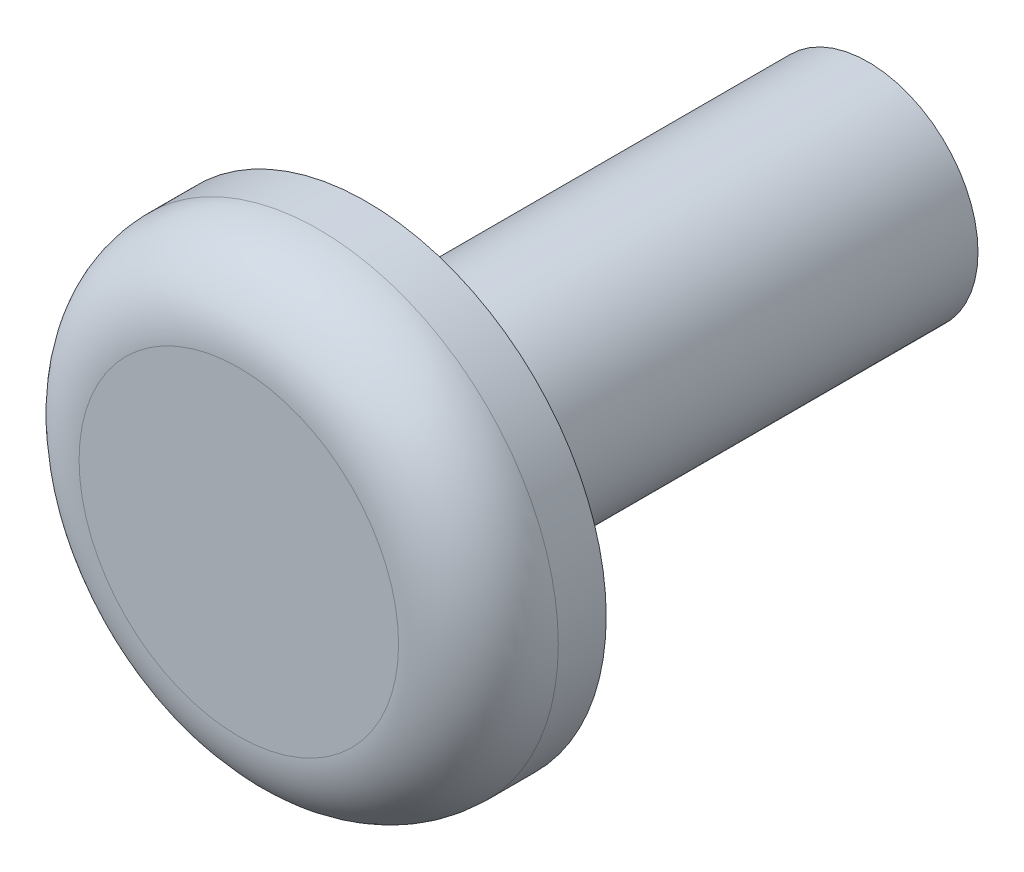
SolidWorks part; units mm, degrees
ref_plane "Front Plane" through (0, 0, 0) normal (0, 0, 1) x (1, 0, 0)
ref_plane "Top Plane" through (0, 0, 0) normal (0, 1, 0) x (1, 0, 0)
ref_plane "Right Plane" through (0, 0, 0) normal (1, 0, 0) x (0, 0, -1)
sketch "Sketch1" plane through (0, 0, 0) normal (0, 0, 1) x (1, 0, 0)
  circle A0 centre (0, 0) radius 3.4375
  dimension "D1" = 6.875
extrude "Boss-Extrude1" add sketch "Sketch1" along normal blind 15.7
sketch "Sketch2" plane through (0, 0, 15.7) normal (0, 0, 1) x (1, 0, 0)
  circle A0 centre (0, 0) radius 7.5
  dimension "D1" = 15
extrude "Boss-Extrude2" add sketch "Sketch2" along normal blind 4
sketch "Sketch3" plane through (0, 0, 0) normal (0, 0, -1) x (-1, 0, 0)
  circle A0 centre (0, 0) radius 1.5
extrude "Cut-Extrude1" cut sketch "Sketch3" against normal blind 5
chamfer "Chamfer1" distance 0.2 distance2 1 1 edges at (-1.5, 0, 0) first distance on face at (-1.5, 0, 0)
fillet "Fillet1" radius 2.5 1 edges at (7.5, 0, 19.7)
